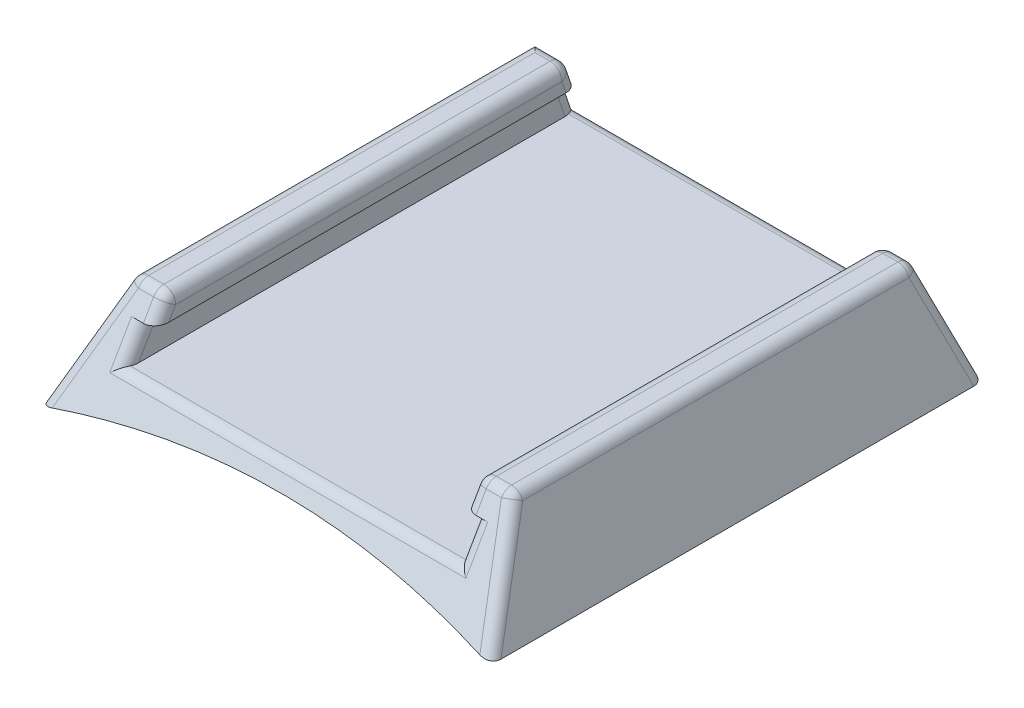
SolidWorks part; units mm, degrees
ref_plane "Front Plane" through (0, 0, 0) normal (0, 0, 1) x (1, 0, 0)
ref_plane "Top Plane" through (0, 0, 0) normal (0, 1, 0) x (1, 0, 0)
ref_plane "Right Plane" through (0, 0, 0) normal (1, 0, 0) x (0, 0, -1)
sketch "Sketch1" plane through (0, 0, 0) normal (0, 0, 1) x (1, 0, 0)
  line L0 (0, 0) -> (3, 8.6267)
  line L1 (3, 8.6267) -> (6, 8.6267)
  line L2 (6, 8.6267) -> (6, 6.6267)
  line L3 (6, 6.6267) -> (5, 6.6267)
  line L4 (5, 6.6267) -> (5, 3.9267)
  line L5 (5, 3.9267) -> (33.2, 3.9267)
  line L7 (19.1, -831.0593) -> (19.1, 39172.7895) construction
  line L8 (33.2, 6.6267) -> (33.2, 3.9267)
  line L9 (32.2, 6.6267) -> (33.2, 6.6267)
  line L10 (32.2, 8.6267) -> (32.2, 6.6267)
  line L11 (35.2, 8.6267) -> (32.2, 8.6267)
  line L12 (38.2, 0) -> (35.2, 8.6267)
  arc A0 (38.2, 0) -> (0, 0) centre (19.1, -73.9511) ccw
  point P8 (40.602, 14.5675)
  point P12 (19.1, 2.4267)
  point P14 (0, 0)
  point P15 (19.1, 3.9267)
  point P20 (0, 0)
  point P21 (34.2, 0)
  point P22 (0, 0)
  point P23 (0, 8.1388)
  point P24 (0.7619, 8.1124)
  point P25 (1.4713, 8.4922)
  dimension "D4" = 76.3778
  dimension "D1" = 28.2
  dimension "D2" = 1
  dimension "D3" = 2.7
  dimension "D5" = 2
  dimension "D6" = 2
  dimension "D7" = 1.5
  dimension "D8" = 3
extrude "Boss-Extrude1" add sketch "Sketch1" along normal blind 42
sketch "Sketch5" plane through (0, 0, 0) normal (1, 0, 0) x (0, 0, -1)
  line L0 (-42, 0) -> (-42, 8.6267)
  line L1 (-42, 8.6267) -> (-37, 8.6267)
  line L2 (-42, 8.6267) -> (0, 8.6267) construction
  line L3 (-37, 8.6267) -> (-42, 0)
  line L4 (0, 0) -> (0, 8.6267)
  line L5 (0, 8.6267) -> (-2.9594, 8.6267)
  line L6 (-2.9594, 8.6267) -> (0, 0)
  dimension "D1" = 5
extrude "Cut-Extrude2" cut sketch "Sketch5" along normal through all
fillet "Fillet1" radius 1 21 edges at (32.2, 7.6267, 2.6164) (33.2, 5.2767, 1.8102) (36.7, 4.3134, 1.4797) (33.7, 8.6267, 2.9594) (3, 8.6267, 19.9797) (4.5, 8.6267, 2.9594) (19.1, 3.9267, 1.3471) (5, 5.2767, 1.8102) (6, 7.6267, 2.6164) (36.7, 4.3134, 39.5) (1.5, 4.3134, 39.5) (35.2, 8.6267, 19.9797) (6, 8.6267, 19.9797) (4.5, 8.6267, 37) (6, 7.6267, 37.5796) (5, 5.2767, 38.9416) (32.2, 8.6267, 19.9797) (33.7, 8.6267, 37) (32.2, 7.6267, 37.5796) (33.2, 5.2767, 38.9416) (19.1, 3.9267, 39.7241)
